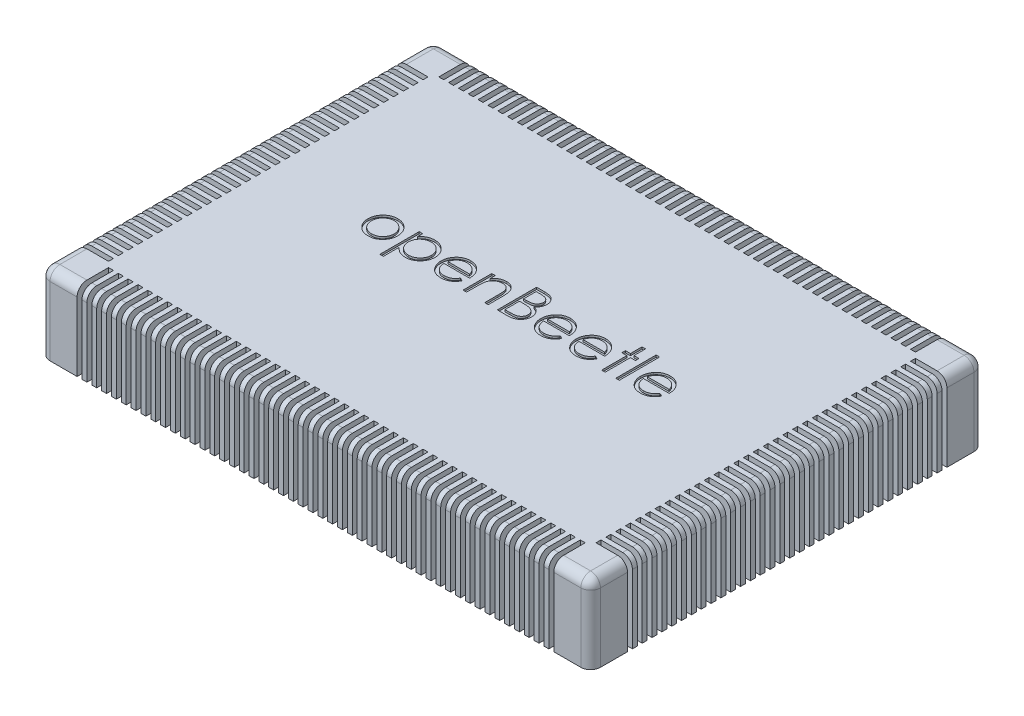
SolidWorks part; units mm, degrees
material "6061-T4 (SS)"
ref_plane "Front Plane" through (0, 0, 0) normal (0, 0, 1) x (1, 0, 0)
ref_plane "Top Plane" through (0, 0, 0) normal (0, 1, 0) x (1, 0, 0)
ref_plane "Right Plane" through (0, 0, 0) normal (1, 0, 0) x (0, 0, -1)
sketch "Sketch1" plane through (0, 0, 0) normal (0, 1, 0) x (1, 0, 0)
  line L0 (-12.7, -12.7) -> (-12.7, 114.3)
  line L1 (0, 0) -> (152.4, 0)
  line L2 (0, 0) -> (0, 101.6)
  line L3 (0, 101.6) -> (152.4, 101.6)
  line L4 (152.4, 0) -> (152.4, 101.6)
  line L5 (-12.7, 114.3) -> (165.1, 114.3)
  line L6 (165.1, -12.7) -> (165.1, 114.3)
  line L7 (-12.7, -12.7) -> (165.1, -12.7)
extrude "Boss-Extrude1" add sketch "Sketch1" along normal blind 12.7
extrude "Boss-Extrude2" add sketch "Sketch1<2>" along normal blind 12.7 from surface contours L7 L6 L5 L0 starting at face at (76.2, 12.7, -50.8)
sketch "Sketch1<2>" plane through (0, 0, 0) normal (0, 1, 0) x (1, 0, 0) same geometry as "Sketch1"
fillet "Fillet4" radius 3.175 8 edges at (165.1, 12.7, 12.7) (-12.7, 12.7, -114.3) (165.1, 12.7, -114.3) (165.1, 25.4, -50.8) (76.2, 25.4, -114.3) (-12.7, 25.4, -50.8) (-12.7, 12.7, 12.7) (76.2, 25.4, 12.7)
sketch "Sketch3" plane through (0, 0, 0) normal (0, 1, 0) x (1, 0, 0)
  line L0 (0.7938, -12.7) -> (0.7938, -2.54)
  line L1 (75.4062, 114.3) -> (76.9938, 114.3)
  line L2 (75.4062, 114.3) -> (75.4062, 104.14)
  line L3 (75.4062, 104.14) -> (76.9938, 104.14)
  line L4 (76.9938, 114.3) -> (76.9938, 104.14)
  line L5 (165.1, 50.0063) -> (154.94, 50.0063)
  line L6 (165.1, 50.0063) -> (165.1, 51.5938)
  line L7 (165.1, 51.5938) -> (154.94, 51.5938)
  line L8 (154.94, 50.0063) -> (154.94, 51.5938)
  line L13 (-0.7938, -2.54) -> (0.7938, -2.54)
  line L14 (-0.7938, -12.7) -> (-0.7938, -2.54)
  line L15 (-0.7938, -12.7) -> (0.7938, -12.7)
  line L16 (76.2, 114.3) -> (76.2, -12.7) construction
  line L17 (165.1, 50.8) -> (-12.7, 50.8) construction
  line L18 (78.5812, 114.3) -> (80.1688, 114.3)
  line L19 (78.5812, 114.3) -> (78.5812, 104.14)
  line L20 (78.5812, 104.14) -> (80.1688, 104.14)
  line L21 (80.1688, 114.3) -> (80.1688, 104.14)
  line L22 (81.7562, 114.3) -> (83.3438, 114.3)
  line L23 (81.7562, 114.3) -> (81.7562, 104.14)
  line L24 (81.7562, 104.14) -> (83.3438, 104.14)
  line L25 (83.3438, 114.3) -> (83.3438, 104.14)
  line L26 (84.9312, 114.3) -> (86.5188, 114.3)
  line L27 (84.9312, 114.3) -> (84.9312, 104.14)
  line L28 (84.9312, 104.14) -> (86.5188, 104.14)
  line L29 (86.5188, 114.3) -> (86.5188, 104.14)
  line L30 (88.1062, 114.3) -> (89.6938, 114.3)
  line L31 (88.1062, 114.3) -> (88.1062, 104.14)
  line L32 (88.1062, 104.14) -> (89.6938, 104.14)
  line L33 (89.6938, 114.3) -> (89.6938, 104.14)
  line L34 (91.2812, 114.3) -> (92.8688, 114.3)
  line L35 (91.2812, 114.3) -> (91.2812, 104.14)
  line L36 (91.2812, 104.14) -> (92.8688, 104.14)
  line L37 (92.8688, 114.3) -> (92.8688, 104.14)
  line L38 (94.4562, 114.3) -> (96.0438, 114.3)
  line L39 (94.4562, 114.3) -> (94.4562, 104.14)
  line L40 (94.4562, 104.14) -> (96.0438, 104.14)
  line L41 (96.0438, 114.3) -> (96.0438, 104.14)
  line L42 (97.6312, 114.3) -> (99.2188, 114.3)
  line L43 (97.6312, 114.3) -> (97.6312, 104.14)
  line L44 (97.6312, 104.14) -> (99.2188, 104.14)
  line L45 (99.2188, 114.3) -> (99.2188, 104.14)
  line L46 (100.8062, 114.3) -> (102.3938, 114.3)
  line L47 (100.8062, 114.3) -> (100.8062, 104.14)
  line L48 (100.8062, 104.14) -> (102.3938, 104.14)
  line L49 (102.3938, 114.3) -> (102.3938, 104.14)
  line L50 (103.9812, 114.3) -> (105.5688, 114.3)
  line L51 (103.9812, 114.3) -> (103.9812, 104.14)
  line L52 (103.9812, 104.14) -> (105.5688, 104.14)
  line L53 (105.5688, 114.3) -> (105.5688, 104.14)
  line L54 (107.1562, 114.3) -> (108.7438, 114.3)
  line L55 (107.1562, 114.3) -> (107.1562, 104.14)
  line L56 (107.1562, 104.14) -> (108.7438, 104.14)
  line L57 (108.7438, 114.3) -> (108.7438, 104.14)
  line L58 (110.3312, 114.3) -> (111.9188, 114.3)
  line L59 (110.3312, 114.3) -> (110.3312, 104.14)
  line L60 (110.3312, 104.14) -> (111.9188, 104.14)
  line L61 (111.9188, 114.3) -> (111.9188, 104.14)
  line L62 (113.5062, 114.3) -> (115.0938, 114.3)
  line L63 (113.5062, 114.3) -> (113.5062, 104.14)
  line L64 (113.5062, 104.14) -> (115.0938, 104.14)
  line L65 (115.0938, 114.3) -> (115.0938, 104.14)
  line L66 (116.6812, 114.3) -> (118.2688, 114.3)
  line L67 (116.6812, 114.3) -> (116.6812, 104.14)
  line L68 (116.6812, 104.14) -> (118.2688, 104.14)
  line L69 (118.2688, 114.3) -> (118.2688, 104.14)
  line L70 (119.8562, 114.3) -> (121.4438, 114.3)
  line L71 (119.8562, 114.3) -> (119.8562, 104.14)
  line L72 (119.8562, 104.14) -> (121.4438, 104.14)
  line L73 (121.4438, 114.3) -> (121.4438, 104.14)
  line L74 (123.0312, 114.3) -> (124.6188, 114.3)
  line L75 (123.0312, 114.3) -> (123.0312, 104.14)
  line L76 (123.0312, 104.14) -> (124.6188, 104.14)
  line L77 (124.6188, 114.3) -> (124.6188, 104.14)
  line L78 (126.2062, 114.3) -> (127.7938, 114.3)
  line L79 (126.2062, 114.3) -> (126.2062, 104.14)
  line L80 (126.2062, 104.14) -> (127.7938, 104.14)
  line L81 (127.7938, 114.3) -> (127.7938, 104.14)
  line L82 (129.3812, 114.3) -> (130.9688, 114.3)
  line L83 (129.3812, 114.3) -> (129.3812, 104.14)
  line L84 (129.3812, 104.14) -> (130.9688, 104.14)
  line L85 (130.9688, 114.3) -> (130.9688, 104.14)
  line L86 (132.5562, 114.3) -> (134.1438, 114.3)
  line L87 (132.5562, 114.3) -> (132.5562, 104.14)
  line L88 (132.5562, 104.14) -> (134.1438, 104.14)
  line L89 (134.1438, 114.3) -> (134.1438, 104.14)
  line L90 (135.7312, 114.3) -> (137.3188, 114.3)
  line L91 (135.7312, 114.3) -> (135.7312, 104.14)
  line L92 (135.7312, 104.14) -> (137.3188, 104.14)
  line L93 (137.3188, 114.3) -> (137.3188, 104.14)
  line L94 (138.9062, 114.3) -> (140.4938, 114.3)
  line L95 (138.9062, 114.3) -> (138.9062, 104.14)
  line L96 (138.9062, 104.14) -> (140.4938, 104.14)
  line L97 (140.4938, 114.3) -> (140.4938, 104.14)
  line L98 (142.0812, 114.3) -> (143.6688, 114.3)
  line L99 (142.0812, 114.3) -> (142.0812, 104.14)
  line L100 (142.0812, 104.14) -> (143.6688, 104.14)
  line L101 (143.6688, 114.3) -> (143.6688, 104.14)
  line L102 (145.2562, 114.3) -> (146.8438, 114.3)
  line L103 (145.2562, 114.3) -> (145.2562, 104.14)
  line L104 (145.2562, 104.14) -> (146.8438, 104.14)
  line L105 (146.8438, 114.3) -> (146.8438, 104.14)
  line L106 (148.4312, 114.3) -> (150.0188, 114.3)
  line L107 (148.4312, 114.3) -> (148.4312, 104.14)
  line L108 (148.4312, 104.14) -> (150.0188, 104.14)
  line L109 (150.0188, 114.3) -> (150.0188, 104.14)
  line L110 (151.6062, 114.3) -> (153.1938, 114.3)
  line L111 (151.6062, 114.3) -> (151.6062, 104.14)
  line L112 (151.6062, 104.14) -> (153.1938, 104.14)
  line L113 (153.1938, 114.3) -> (153.1938, 104.14)
  line L114 (72.2312, 114.3) -> (73.8188, 114.3)
  line L115 (72.2312, 114.3) -> (72.2312, 104.14)
  line L116 (72.2312, 104.14) -> (73.8188, 104.14)
  line L117 (73.8188, 114.3) -> (73.8188, 104.14)
  line L118 (69.0562, 114.3) -> (70.6438, 114.3)
  line L119 (69.0562, 114.3) -> (69.0562, 104.14)
  line L120 (69.0562, 104.14) -> (70.6438, 104.14)
  line L121 (70.6438, 114.3) -> (70.6438, 104.14)
  line L122 (65.8812, 114.3) -> (67.4688, 114.3)
  line L123 (65.8812, 114.3) -> (65.8812, 104.14)
  line L124 (65.8812, 104.14) -> (67.4688, 104.14)
  line L125 (67.4688, 114.3) -> (67.4688, 104.14)
  line L126 (62.7062, 114.3) -> (64.2938, 114.3)
  line L127 (62.7062, 114.3) -> (62.7062, 104.14)
  line L128 (62.7062, 104.14) -> (64.2938, 104.14)
  line L129 (64.2938, 114.3) -> (64.2938, 104.14)
  line L130 (59.5312, 114.3) -> (61.1188, 114.3)
  line L131 (59.5312, 114.3) -> (59.5312, 104.14)
  line L132 (59.5312, 104.14) -> (61.1188, 104.14)
  line L133 (61.1188, 114.3) -> (61.1188, 104.14)
  line L134 (56.3562, 114.3) -> (57.9438, 114.3)
  line L135 (56.3562, 114.3) -> (56.3562, 104.14)
  line L136 (56.3562, 104.14) -> (57.9438, 104.14)
  line L137 (57.9438, 114.3) -> (57.9438, 104.14)
  line L138 (53.1812, 114.3) -> (54.7688, 114.3)
  line L139 (53.1812, 114.3) -> (53.1812, 104.14)
  line L140 (53.1812, 104.14) -> (54.7688, 104.14)
  line L141 (54.7688, 114.3) -> (54.7688, 104.14)
  line L142 (50.0062, 114.3) -> (51.5938, 114.3)
  line L143 (50.0062, 114.3) -> (50.0062, 104.14)
  line L144 (50.0062, 104.14) -> (51.5938, 104.14)
  line L145 (51.5938, 114.3) -> (51.5938, 104.14)
  line L146 (46.8312, 114.3) -> (48.4188, 114.3)
  line L147 (46.8312, 114.3) -> (46.8312, 104.14)
  line L148 (46.8312, 104.14) -> (48.4188, 104.14)
  line L149 (48.4188, 114.3) -> (48.4188, 104.14)
  line L150 (43.6562, 114.3) -> (45.2438, 114.3)
  line L151 (43.6562, 114.3) -> (43.6562, 104.14)
  line L152 (43.6562, 104.14) -> (45.2438, 104.14)
  line L153 (45.2438, 114.3) -> (45.2438, 104.14)
  line L154 (40.4812, 114.3) -> (42.0688, 114.3)
  line L155 (40.4812, 114.3) -> (40.4812, 104.14)
  line L156 (40.4812, 104.14) -> (42.0688, 104.14)
  line L157 (42.0688, 114.3) -> (42.0688, 104.14)
  line L158 (37.3062, 114.3) -> (38.8938, 114.3)
  line L159 (37.3062, 114.3) -> (37.3062, 104.14)
  line L160 (37.3062, 104.14) -> (38.8938, 104.14)
  line L161 (38.8938, 114.3) -> (38.8938, 104.14)
  line L162 (34.1312, 114.3) -> (35.7188, 114.3)
  line L163 (34.1312, 114.3) -> (34.1312, 104.14)
  line L164 (34.1312, 104.14) -> (35.7188, 104.14)
  line L165 (35.7188, 114.3) -> (35.7188, 104.14)
  line L166 (30.9562, 114.3) -> (32.5438, 114.3)
  line L167 (30.9562, 114.3) -> (30.9562, 104.14)
  line L168 (30.9562, 104.14) -> (32.5438, 104.14)
  line L169 (32.5438, 114.3) -> (32.5438, 104.14)
  line L170 (27.7812, 114.3) -> (29.3688, 114.3)
  line L171 (27.7812, 114.3) -> (27.7812, 104.14)
  line L172 (27.7812, 104.14) -> (29.3688, 104.14)
  line L173 (29.3688, 114.3) -> (29.3688, 104.14)
  line L174 (24.6062, 114.3) -> (26.1938, 114.3)
  line L175 (24.6062, 114.3) -> (24.6062, 104.14)
  line L176 (24.6062, 104.14) -> (26.1938, 104.14)
  line L177 (26.1938, 114.3) -> (26.1938, 104.14)
  line L178 (21.4312, 114.3) -> (23.0188, 114.3)
  line L179 (21.4312, 114.3) -> (21.4312, 104.14)
  line L180 (21.4312, 104.14) -> (23.0188, 104.14)
  line L181 (23.0188, 114.3) -> (23.0188, 104.14)
  line L182 (18.2562, 114.3) -> (19.8438, 114.3)
  line L183 (18.2562, 114.3) -> (18.2562, 104.14)
  line L184 (18.2562, 104.14) -> (19.8438, 104.14)
  line L185 (19.8438, 114.3) -> (19.8438, 104.14)
  line L186 (15.0812, 114.3) -> (16.6688, 114.3)
  line L187 (15.0812, 114.3) -> (15.0812, 104.14)
  line L188 (15.0812, 104.14) -> (16.6688, 104.14)
  line L189 (16.6688, 114.3) -> (16.6688, 104.14)
  line L190 (11.9062, 114.3) -> (13.4938, 114.3)
  line L191 (11.9062, 114.3) -> (11.9062, 104.14)
  line L192 (11.9062, 104.14) -> (13.4938, 104.14)
  line L193 (13.4938, 114.3) -> (13.4938, 104.14)
  line L194 (8.7312, 114.3) -> (10.3188, 114.3)
  line L195 (8.7312, 114.3) -> (8.7312, 104.14)
  line L196 (8.7312, 104.14) -> (10.3188, 104.14)
  line L197 (10.3188, 114.3) -> (10.3188, 104.14)
  line L198 (5.5562, 114.3) -> (7.1438, 114.3)
  line L199 (5.5562, 114.3) -> (5.5562, 104.14)
  line L200 (5.5562, 104.14) -> (7.1438, 104.14)
  line L201 (7.1438, 114.3) -> (7.1438, 104.14)
  line L202 (2.3812, 114.3) -> (3.9688, 114.3)
  line L203 (2.3812, 114.3) -> (2.3812, 104.14)
  line L204 (2.3812, 104.14) -> (3.9688, 104.14)
  line L205 (3.9688, 114.3) -> (3.9688, 104.14)
  line L206 (-0.7938, 114.3) -> (0.7938, 114.3)
  line L207 (-0.7938, 114.3) -> (-0.7938, 104.14)
  line L208 (-0.7938, 104.14) -> (0.7938, 104.14)
  line L209 (0.7938, 114.3) -> (0.7938, 104.14)
  line L210 (165.1, 53.1813) -> (154.94, 53.1813)
  line L211 (165.1, 53.1813) -> (165.1, 54.7688)
  line L212 (165.1, 54.7688) -> (154.94, 54.7688)
  line L213 (154.94, 53.1813) -> (154.94, 54.7688)
  line L214 (165.1, 56.3563) -> (154.94, 56.3563)
  line L215 (165.1, 56.3563) -> (165.1, 57.9438)
  line L216 (165.1, 57.9438) -> (154.94, 57.9438)
  line L217 (154.94, 56.3563) -> (154.94, 57.9438)
  line L218 (165.1, 59.5313) -> (154.94, 59.5313)
  line L219 (165.1, 59.5313) -> (165.1, 61.1188)
  line L220 (165.1, 61.1188) -> (154.94, 61.1188)
  line L221 (154.94, 59.5313) -> (154.94, 61.1188)
  line L222 (165.1, 62.7063) -> (154.94, 62.7063)
  line L223 (165.1, 62.7063) -> (165.1, 64.2938)
  line L224 (165.1, 64.2938) -> (154.94, 64.2938)
  line L225 (154.94, 62.7063) -> (154.94, 64.2938)
  line L226 (165.1, 65.8813) -> (154.94, 65.8813)
  line L227 (165.1, 65.8813) -> (165.1, 67.4688)
  line L228 (165.1, 67.4688) -> (154.94, 67.4688)
  line L229 (154.94, 65.8813) -> (154.94, 67.4688)
  line L230 (165.1, 69.0563) -> (154.94, 69.0563)
  line L231 (165.1, 69.0563) -> (165.1, 70.6438)
  line L232 (165.1, 70.6438) -> (154.94, 70.6438)
  line L233 (154.94, 69.0563) -> (154.94, 70.6438)
  line L234 (165.1, 72.2313) -> (154.94, 72.2313)
  line L235 (165.1, 72.2313) -> (165.1, 73.8188)
  line L236 (165.1, 73.8188) -> (154.94, 73.8188)
  line L237 (154.94, 72.2313) -> (154.94, 73.8188)
  line L238 (165.1, 75.4063) -> (154.94, 75.4063)
  line L239 (165.1, 75.4063) -> (165.1, 76.9938)
  line L240 (165.1, 76.9938) -> (154.94, 76.9938)
  line L241 (154.94, 75.4063) -> (154.94, 76.9938)
  line L242 (165.1, 78.5813) -> (154.94, 78.5813)
  line L243 (165.1, 78.5813) -> (165.1, 80.1688)
  line L244 (165.1, 80.1688) -> (154.94, 80.1688)
  line L245 (154.94, 78.5813) -> (154.94, 80.1688)
  line L246 (165.1, 81.7563) -> (154.94, 81.7563)
  line L247 (165.1, 81.7563) -> (165.1, 83.3438)
  line L248 (165.1, 83.3438) -> (154.94, 83.3438)
  line L249 (154.94, 81.7563) -> (154.94, 83.3438)
  line L250 (165.1, 84.9313) -> (154.94, 84.9313)
  line L251 (165.1, 84.9313) -> (165.1, 86.5188)
  line L252 (165.1, 86.5188) -> (154.94, 86.5188)
  line L253 (154.94, 84.9313) -> (154.94, 86.5188)
  line L254 (165.1, 88.1063) -> (154.94, 88.1063)
  line L255 (165.1, 88.1063) -> (165.1, 89.6938)
  line L256 (165.1, 89.6938) -> (154.94, 89.6938)
  line L257 (154.94, 88.1063) -> (154.94, 89.6938)
  line L258 (165.1, 91.2813) -> (154.94, 91.2813)
  line L259 (165.1, 91.2813) -> (165.1, 92.8688)
  line L260 (165.1, 92.8688) -> (154.94, 92.8688)
  line L261 (154.94, 91.2813) -> (154.94, 92.8688)
  line L262 (165.1, 94.4563) -> (154.94, 94.4563)
  line L263 (165.1, 94.4563) -> (165.1, 96.0438)
  line L264 (165.1, 96.0438) -> (154.94, 96.0438)
  line L265 (154.94, 94.4563) -> (154.94, 96.0438)
  line L266 (165.1, 97.6313) -> (154.94, 97.6313)
  line L267 (165.1, 97.6313) -> (165.1, 99.2188)
  line L268 (165.1, 99.2188) -> (154.94, 99.2188)
  line L269 (154.94, 97.6313) -> (154.94, 99.2188)
  line L270 (165.1, 100.8063) -> (154.94, 100.8063)
  line L271 (165.1, 100.8063) -> (165.1, 102.3938)
  line L272 (165.1, 102.3938) -> (154.94, 102.3938)
  line L273 (154.94, 100.8063) -> (154.94, 102.3938)
  line L274 (165.1, 46.8313) -> (154.94, 46.8313)
  line L275 (165.1, 46.8313) -> (165.1, 48.4188)
  line L276 (165.1, 48.4188) -> (154.94, 48.4188)
  line L277 (154.94, 46.8313) -> (154.94, 48.4188)
  line L278 (165.1, 43.6563) -> (154.94, 43.6563)
  line L279 (165.1, 43.6563) -> (165.1, 45.2438)
  line L280 (165.1, 45.2438) -> (154.94, 45.2438)
  line L281 (154.94, 43.6563) -> (154.94, 45.2438)
  line L282 (165.1, 40.4813) -> (154.94, 40.4813)
  line L283 (165.1, 40.4813) -> (165.1, 42.0688)
  line L284 (165.1, 42.0688) -> (154.94, 42.0688)
  line L285 (154.94, 40.4813) -> (154.94, 42.0688)
  line L286 (165.1, 37.3063) -> (154.94, 37.3063)
  line L287 (165.1, 37.3063) -> (165.1, 38.8938)
  line L288 (165.1, 38.8938) -> (154.94, 38.8938)
  line L289 (154.94, 37.3063) -> (154.94, 38.8938)
  line L290 (165.1, 34.1313) -> (154.94, 34.1313)
  line L291 (165.1, 34.1313) -> (165.1, 35.7188)
  line L292 (165.1, 35.7188) -> (154.94, 35.7188)
  line L293 (154.94, 34.1313) -> (154.94, 35.7188)
  line L294 (165.1, 30.9563) -> (154.94, 30.9563)
  line L295 (165.1, 30.9563) -> (165.1, 32.5438)
  line L296 (165.1, 32.5438) -> (154.94, 32.5438)
  line L297 (154.94, 30.9563) -> (154.94, 32.5438)
  line L298 (165.1, 27.7813) -> (154.94, 27.7813)
  line L299 (165.1, 27.7813) -> (165.1, 29.3688)
  line L300 (165.1, 29.3688) -> (154.94, 29.3688)
  line L301 (154.94, 27.7813) -> (154.94, 29.3688)
  line L302 (165.1, 24.6063) -> (154.94, 24.6063)
  line L303 (165.1, 24.6063) -> (165.1, 26.1938)
  line L304 (165.1, 26.1938) -> (154.94, 26.1938)
  line L305 (154.94, 24.6063) -> (154.94, 26.1938)
  line L306 (165.1, 21.4313) -> (154.94, 21.4313)
  line L307 (165.1, 21.4313) -> (165.1, 23.0188)
  line L308 (165.1, 23.0188) -> (154.94, 23.0188)
  line L309 (154.94, 21.4313) -> (154.94, 23.0188)
  line L310 (165.1, 18.2563) -> (154.94, 18.2563)
  line L311 (165.1, 18.2563) -> (165.1, 19.8438)
  line L312 (165.1, 19.8438) -> (154.94, 19.8438)
  line L313 (154.94, 18.2563) -> (154.94, 19.8438)
  line L314 (165.1, 15.0813) -> (154.94, 15.0813)
  line L315 (165.1, 15.0813) -> (165.1, 16.6688)
  line L316 (165.1, 16.6688) -> (154.94, 16.6688)
  line L317 (154.94, 15.0813) -> (154.94, 16.6688)
  line L318 (165.1, 11.9063) -> (154.94, 11.9063)
  line L319 (165.1, 11.9063) -> (165.1, 13.4938)
  line L320 (165.1, 13.4938) -> (154.94, 13.4938)
  line L321 (154.94, 11.9063) -> (154.94, 13.4938)
  line L322 (165.1, 8.7313) -> (154.94, 8.7313)
  line L323 (165.1, 8.7313) -> (165.1, 10.3188)
  line L324 (165.1, 10.3188) -> (154.94, 10.3188)
  line L325 (154.94, 8.7313) -> (154.94, 10.3188)
  line L326 (165.1, 5.5563) -> (154.94, 5.5563)
  line L327 (165.1, 5.5563) -> (165.1, 7.1438)
  line L328 (165.1, 7.1438) -> (154.94, 7.1438)
  line L329 (154.94, 5.5563) -> (154.94, 7.1438)
  line L330 (165.1, 2.3813) -> (154.94, 2.3813)
  line L331 (165.1, 2.3813) -> (165.1, 3.9688)
  line L332 (165.1, 3.9688) -> (154.94, 3.9688)
  line L333 (154.94, 2.3813) -> (154.94, 3.9688)
  line L334 (165.1, -0.7937) -> (154.94, -0.7937)
  line L335 (165.1, -0.7937) -> (165.1, 0.7938)
  line L336 (165.1, 0.7938) -> (154.94, 0.7938)
  line L337 (154.94, -0.7937) -> (154.94, 0.7938)
  line L338 (3.9688, -12.7) -> (3.9688, -2.54)
  line L339 (2.3812, -2.54) -> (3.9688, -2.54)
  line L340 (2.3812, -12.7) -> (2.3812, -2.54)
  line L341 (2.3812, -12.7) -> (3.9688, -12.7)
  line L342 (7.1438, -12.7) -> (7.1438, -2.54)
  line L343 (5.5562, -2.54) -> (7.1438, -2.54)
  line L344 (5.5562, -12.7) -> (5.5562, -2.54)
  line L345 (5.5562, -12.7) -> (7.1438, -12.7)
  line L346 (10.3188, -12.7) -> (10.3188, -2.54)
  line L347 (8.7312, -2.54) -> (10.3188, -2.54)
  line L348 (8.7312, -12.7) -> (8.7312, -2.54)
  line L349 (8.7312, -12.7) -> (10.3188, -12.7)
  line L350 (13.4938, -12.7) -> (13.4938, -2.54)
  line L351 (11.9062, -2.54) -> (13.4938, -2.54)
  line L352 (11.9062, -12.7) -> (11.9062, -2.54)
  line L353 (11.9062, -12.7) -> (13.4938, -12.7)
  line L354 (16.6688, -12.7) -> (16.6688, -2.54)
  line L355 (15.0812, -2.54) -> (16.6688, -2.54)
  line L356 (15.0812, -12.7) -> (15.0812, -2.54)
  line L357 (15.0812, -12.7) -> (16.6688, -12.7)
  line L358 (19.8438, -12.7) -> (19.8438, -2.54)
  line L359 (18.2562, -2.54) -> (19.8438, -2.54)
  line L360 (18.2562, -12.7) -> (18.2562, -2.54)
  line L361 (18.2562, -12.7) -> (19.8438, -12.7)
  line L362 (23.0188, -12.7) -> (23.0188, -2.54)
  line L363 (21.4312, -2.54) -> (23.0188, -2.54)
  line L364 (21.4312, -12.7) -> (21.4312, -2.54)
  line L365 (21.4312, -12.7) -> (23.0188, -12.7)
  line L366 (26.1938, -12.7) -> (26.1938, -2.54)
  line L367 (24.6062, -2.54) -> (26.1938, -2.54)
  line L368 (24.6062, -12.7) -> (24.6062, -2.54)
  line L369 (24.6062, -12.7) -> (26.1938, -12.7)
  line L370 (29.3688, -12.7) -> (29.3688, -2.54)
  line L371 (27.7812, -2.54) -> (29.3688, -2.54)
  line L372 (27.7812, -12.7) -> (27.7812, -2.54)
  line L373 (27.7812, -12.7) -> (29.3688, -12.7)
  line L374 (32.5438, -12.7) -> (32.5438, -2.54)
  line L375 (30.9562, -2.54) -> (32.5438, -2.54)
  line L376 (30.9562, -12.7) -> (30.9562, -2.54)
  line L377 (30.9562, -12.7) -> (32.5438, -12.7)
  line L378 (35.7188, -12.7) -> (35.7188, -2.54)
  line L379 (34.1312, -2.54) -> (35.7188, -2.54)
  line L380 (34.1312, -12.7) -> (34.1312, -2.54)
  line L381 (34.1312, -12.7) -> (35.7188, -12.7)
  line L382 (38.8938, -12.7) -> (38.8938, -2.54)
  line L383 (37.3062, -2.54) -> (38.8938, -2.54)
  line L384 (37.3062, -12.7) -> (37.3062, -2.54)
  line L385 (37.3062, -12.7) -> (38.8938, -12.7)
  line L386 (42.0688, -12.7) -> (42.0688, -2.54)
  line L387 (40.4812, -2.54) -> (42.0688, -2.54)
  line L388 (40.4812, -12.7) -> (40.4812, -2.54)
  line L389 (40.4812, -12.7) -> (42.0688, -12.7)
  line L390 (45.2438, -12.7) -> (45.2438, -2.54)
  line L391 (43.6562, -2.54) -> (45.2438, -2.54)
  line L392 (43.6562, -12.7) -> (43.6562, -2.54)
  line L393 (43.6562, -12.7) -> (45.2438, -12.7)
  line L394 (48.4188, -12.7) -> (48.4188, -2.54)
  line L395 (46.8312, -2.54) -> (48.4188, -2.54)
  line L396 (46.8312, -12.7) -> (46.8312, -2.54)
  line L397 (46.8312, -12.7) -> (48.4188, -12.7)
  line L398 (51.5938, -12.7) -> (51.5938, -2.54)
  line L399 (50.0062, -2.54) -> (51.5938, -2.54)
  line L400 (50.0062, -12.7) -> (50.0062, -2.54)
  line L401 (50.0062, -12.7) -> (51.5938, -12.7)
  line L402 (54.7688, -12.7) -> (54.7688, -2.54)
  line L403 (53.1812, -2.54) -> (54.7688, -2.54)
  line L404 (53.1812, -12.7) -> (53.1812, -2.54)
  line L405 (53.1812, -12.7) -> (54.7688, -12.7)
  line L406 (57.9438, -12.7) -> (57.9438, -2.54)
  line L407 (56.3562, -2.54) -> (57.9438, -2.54)
  line L408 (56.3562, -12.7) -> (56.3562, -2.54)
  line L409 (56.3562, -12.7) -> (57.9438, -12.7)
  line L410 (61.1188, -12.7) -> (61.1188, -2.54)
  line L411 (59.5312, -2.54) -> (61.1188, -2.54)
  line L412 (59.5312, -12.7) -> (59.5312, -2.54)
  line L413 (59.5312, -12.7) -> (61.1188, -12.7)
  line L414 (64.2938, -12.7) -> (64.2938, -2.54)
  line L415 (62.7062, -2.54) -> (64.2938, -2.54)
  line L416 (62.7062, -12.7) -> (62.7062, -2.54)
  line L417 (62.7062, -12.7) -> (64.2938, -12.7)
  line L418 (67.4688, -12.7) -> (67.4688, -2.54)
  line L419 (65.8812, -2.54) -> (67.4688, -2.54)
  line L420 (65.8812, -12.7) -> (65.8812, -2.54)
  line L421 (65.8812, -12.7) -> (67.4688, -12.7)
  line L422 (70.6438, -12.7) -> (70.6438, -2.54)
  line L423 (69.0562, -2.54) -> (70.6438, -2.54)
  line L424 (69.0562, -12.7) -> (69.0562, -2.54)
  line L425 (69.0562, -12.7) -> (70.6438, -12.7)
  line L426 (73.8188, -12.7) -> (73.8188, -2.54)
  line L427 (72.2312, -2.54) -> (73.8188, -2.54)
  line L428 (72.2312, -12.7) -> (72.2312, -2.54)
  line L429 (72.2312, -12.7) -> (73.8188, -12.7)
  line L430 (153.1938, -12.7) -> (153.1938, -2.54)
  line L431 (151.6062, -2.54) -> (153.1938, -2.54)
  line L432 (151.6062, -12.7) -> (151.6062, -2.54)
  line L433 (151.6062, -12.7) -> (153.1938, -12.7)
  line L434 (150.0188, -12.7) -> (150.0188, -2.54)
  line L435 (148.4312, -2.54) -> (150.0188, -2.54)
  line L436 (148.4312, -12.7) -> (148.4312, -2.54)
  line L437 (148.4312, -12.7) -> (150.0188, -12.7)
  line L438 (146.8438, -12.7) -> (146.8438, -2.54)
  line L439 (145.2562, -2.54) -> (146.8438, -2.54)
  line L440 (145.2562, -12.7) -> (145.2562, -2.54)
  line L441 (145.2562, -12.7) -> (146.8438, -12.7)
  line L442 (143.6688, -12.7) -> (143.6688, -2.54)
  line L443 (142.0812, -2.54) -> (143.6688, -2.54)
  line L444 (142.0812, -12.7) -> (142.0812, -2.54)
  line L445 (142.0812, -12.7) -> (143.6688, -12.7)
  line L446 (140.4938, -12.7) -> (140.4938, -2.54)
  line L447 (138.9062, -2.54) -> (140.4938, -2.54)
  line L448 (138.9062, -12.7) -> (138.9062, -2.54)
  line L449 (138.9062, -12.7) -> (140.4938, -12.7)
  line L450 (137.3188, -12.7) -> (137.3188, -2.54)
  line L451 (135.7312, -2.54) -> (137.3188, -2.54)
  line L452 (135.7312, -12.7) -> (135.7312, -2.54)
  line L453 (135.7312, -12.7) -> (137.3188, -12.7)
  line L454 (134.1438, -12.7) -> (134.1438, -2.54)
  line L455 (132.5562, -2.54) -> (134.1438, -2.54)
  line L456 (132.5562, -12.7) -> (132.5562, -2.54)
  line L457 (132.5562, -12.7) -> (134.1438, -12.7)
  line L458 (130.9688, -12.7) -> (130.9688, -2.54)
  line L459 (129.3812, -2.54) -> (130.9688, -2.54)
  line L460 (129.3812, -12.7) -> (129.3812, -2.54)
  line L461 (129.3812, -12.7) -> (130.9688, -12.7)
  line L462 (127.7938, -12.7) -> (127.7938, -2.54)
  line L463 (126.2062, -2.54) -> (127.7938, -2.54)
  line L464 (126.2062, -12.7) -> (126.2062, -2.54)
  line L465 (126.2062, -12.7) -> (127.7938, -12.7)
  line L466 (124.6188, -12.7) -> (124.6188, -2.54)
  line L467 (123.0312, -2.54) -> (124.6188, -2.54)
  line L468 (123.0312, -12.7) -> (123.0312, -2.54)
  line L469 (123.0312, -12.7) -> (124.6188, -12.7)
  line L470 (121.4438, -12.7) -> (121.4438, -2.54)
  line L471 (119.8562, -2.54) -> (121.4438, -2.54)
  line L472 (119.8562, -12.7) -> (119.8562, -2.54)
  line L473 (119.8562, -12.7) -> (121.4438, -12.7)
  line L474 (118.2688, -12.7) -> (118.2688, -2.54)
  line L475 (116.6812, -2.54) -> (118.2688, -2.54)
  line L476 (116.6812, -12.7) -> (116.6812, -2.54)
  line L477 (116.6812, -12.7) -> (118.2688, -12.7)
  line L478 (115.0938, -12.7) -> (115.0938, -2.54)
  line L479 (113.5062, -2.54) -> (115.0938, -2.54)
  line L480 (113.5062, -12.7) -> (113.5062, -2.54)
  line L481 (113.5062, -12.7) -> (115.0938, -12.7)
  line L482 (111.9188, -12.7) -> (111.9188, -2.54)
  line L483 (110.3312, -2.54) -> (111.9188, -2.54)
  line L484 (110.3312, -12.7) -> (110.3312, -2.54)
  line L485 (110.3312, -12.7) -> (111.9188, -12.7)
  line L486 (108.7438, -12.7) -> (108.7438, -2.54)
  line L487 (107.1562, -2.54) -> (108.7438, -2.54)
  line L488 (107.1562, -12.7) -> (107.1562, -2.54)
  line L489 (107.1562, -12.7) -> (108.7438, -12.7)
  line L490 (105.5688, -12.7) -> (105.5688, -2.54)
  line L491 (103.9812, -2.54) -> (105.5688, -2.54)
  line L492 (103.9812, -12.7) -> (103.9812, -2.54)
  line L493 (103.9812, -12.7) -> (105.5688, -12.7)
  line L494 (102.3938, -12.7) -> (102.3938, -2.54)
  line L495 (100.8062, -2.54) -> (102.3938, -2.54)
  line L496 (100.8062, -12.7) -> (100.8062, -2.54)
  line L497 (100.8062, -12.7) -> (102.3938, -12.7)
  line L498 (99.2188, -12.7) -> (99.2188, -2.54)
  line L499 (97.6312, -2.54) -> (99.2188, -2.54)
  line L500 (97.6312, -12.7) -> (97.6312, -2.54)
  line L501 (97.6312, -12.7) -> (99.2188, -12.7)
  line L502 (96.0438, -12.7) -> (96.0438, -2.54)
  line L503 (94.4562, -2.54) -> (96.0438, -2.54)
  line L504 (94.4562, -12.7) -> (94.4562, -2.54)
  line L505 (94.4562, -12.7) -> (96.0438, -12.7)
  line L506 (92.8688, -12.7) -> (92.8688, -2.54)
  line L507 (91.2812, -2.54) -> (92.8688, -2.54)
  line L508 (91.2812, -12.7) -> (91.2812, -2.54)
  line L509 (91.2812, -12.7) -> (92.8688, -12.7)
  line L510 (89.6938, -12.7) -> (89.6938, -2.54)
  line L511 (88.1062, -2.54) -> (89.6938, -2.54)
  line L512 (88.1062, -12.7) -> (88.1062, -2.54)
  line L513 (88.1062, -12.7) -> (89.6938, -12.7)
  line L514 (86.5188, -12.7) -> (86.5188, -2.54)
  line L515 (84.9312, -2.54) -> (86.5188, -2.54)
  line L516 (84.9312, -12.7) -> (84.9312, -2.54)
  line L517 (84.9312, -12.7) -> (86.5188, -12.7)
  line L518 (83.3438, -12.7) -> (83.3438, -2.54)
  line L519 (81.7562, -2.54) -> (83.3438, -2.54)
  line L520 (81.7562, -12.7) -> (81.7562, -2.54)
  line L521 (81.7562, -12.7) -> (83.3438, -12.7)
  line L522 (80.1688, -12.7) -> (80.1688, -2.54)
  line L523 (78.5812, -2.54) -> (80.1688, -2.54)
  line L524 (78.5812, -12.7) -> (78.5812, -2.54)
  line L525 (78.5812, -12.7) -> (80.1688, -12.7)
  line L526 (76.9938, -12.7) -> (76.9938, -2.54)
  line L527 (75.4062, -2.54) -> (76.9938, -2.54)
  line L528 (75.4062, -12.7) -> (75.4062, -2.54)
  line L529 (75.4062, -12.7) -> (76.9938, -12.7)
  line L530 (-2.54, -0.7937) -> (-2.54, 0.7938)
  line L531 (-12.7, 0.7938) -> (-2.54, 0.7938)
  line L532 (-12.7, -0.7937) -> (-12.7, 0.7938)
  line L533 (-12.7, -0.7937) -> (-2.54, -0.7937)
  line L534 (-2.54, 2.3813) -> (-2.54, 3.9688)
  line L535 (-12.7, 3.9688) -> (-2.54, 3.9688)
  line L536 (-12.7, 2.3813) -> (-12.7, 3.9688)
  line L537 (-12.7, 2.3813) -> (-2.54, 2.3813)
  line L538 (-2.54, 5.5563) -> (-2.54, 7.1438)
  line L539 (-12.7, 7.1438) -> (-2.54, 7.1438)
  line L540 (-12.7, 5.5563) -> (-12.7, 7.1438)
  line L541 (-12.7, 5.5563) -> (-2.54, 5.5563)
  line L542 (-2.54, 8.7313) -> (-2.54, 10.3188)
  line L543 (-12.7, 10.3188) -> (-2.54, 10.3188)
  line L544 (-12.7, 8.7313) -> (-12.7, 10.3188)
  line L545 (-12.7, 8.7313) -> (-2.54, 8.7313)
  line L546 (-2.54, 11.9063) -> (-2.54, 13.4938)
  line L547 (-12.7, 13.4938) -> (-2.54, 13.4938)
  line L548 (-12.7, 11.9063) -> (-12.7, 13.4938)
  line L549 (-12.7, 11.9063) -> (-2.54, 11.9063)
  line L550 (-2.54, 15.0813) -> (-2.54, 16.6688)
  line L551 (-12.7, 16.6688) -> (-2.54, 16.6688)
  line L552 (-12.7, 15.0813) -> (-12.7, 16.6688)
  line L553 (-12.7, 15.0813) -> (-2.54, 15.0813)
  line L554 (-2.54, 18.2563) -> (-2.54, 19.8438)
  line L555 (-12.7, 19.8438) -> (-2.54, 19.8438)
  line L556 (-12.7, 18.2563) -> (-12.7, 19.8438)
  line L557 (-12.7, 18.2563) -> (-2.54, 18.2563)
  line L558 (-2.54, 21.4313) -> (-2.54, 23.0188)
  line L559 (-12.7, 23.0188) -> (-2.54, 23.0188)
  line L560 (-12.7, 21.4313) -> (-12.7, 23.0188)
  line L561 (-12.7, 21.4313) -> (-2.54, 21.4313)
  line L562 (-2.54, 24.6063) -> (-2.54, 26.1938)
  line L563 (-12.7, 26.1938) -> (-2.54, 26.1938)
  line L564 (-12.7, 24.6063) -> (-12.7, 26.1938)
  line L565 (-12.7, 24.6063) -> (-2.54, 24.6063)
  line L566 (-2.54, 27.7813) -> (-2.54, 29.3688)
  line L567 (-12.7, 29.3688) -> (-2.54, 29.3688)
  line L568 (-12.7, 27.7813) -> (-12.7, 29.3688)
  line L569 (-12.7, 27.7813) -> (-2.54, 27.7813)
  line L570 (-2.54, 30.9563) -> (-2.54, 32.5438)
  line L571 (-12.7, 32.5438) -> (-2.54, 32.5438)
  line L572 (-12.7, 30.9563) -> (-12.7, 32.5438)
  line L573 (-12.7, 30.9563) -> (-2.54, 30.9563)
  line L574 (-2.54, 34.1313) -> (-2.54, 35.7188)
  line L575 (-12.7, 35.7188) -> (-2.54, 35.7188)
  line L576 (-12.7, 34.1313) -> (-12.7, 35.7188)
  line L577 (-12.7, 34.1313) -> (-2.54, 34.1313)
  line L578 (-2.54, 37.3063) -> (-2.54, 38.8938)
  line L579 (-12.7, 38.8938) -> (-2.54, 38.8938)
  line L580 (-12.7, 37.3063) -> (-12.7, 38.8938)
  line L581 (-12.7, 37.3063) -> (-2.54, 37.3063)
  line L582 (-2.54, 40.4813) -> (-2.54, 42.0688)
  line L583 (-12.7, 42.0688) -> (-2.54, 42.0688)
  line L584 (-12.7, 40.4813) -> (-12.7, 42.0688)
  line L585 (-12.7, 40.4813) -> (-2.54, 40.4813)
  line L586 (-2.54, 43.6563) -> (-2.54, 45.2438)
  line L587 (-12.7, 45.2438) -> (-2.54, 45.2438)
  line L588 (-12.7, 43.6563) -> (-12.7, 45.2438)
  line L589 (-12.7, 43.6563) -> (-2.54, 43.6563)
  line L590 (-2.54, 46.8313) -> (-2.54, 48.4188)
  line L591 (-12.7, 48.4188) -> (-2.54, 48.4188)
  line L592 (-12.7, 46.8313) -> (-12.7, 48.4188)
  line L593 (-12.7, 46.8313) -> (-2.54, 46.8313)
  line L594 (-2.54, 100.8063) -> (-2.54, 102.3938)
  line L595 (-12.7, 102.3938) -> (-2.54, 102.3938)
  line L596 (-12.7, 100.8063) -> (-12.7, 102.3938)
  line L597 (-12.7, 100.8063) -> (-2.54, 100.8063)
  line L598 (-2.54, 97.6313) -> (-2.54, 99.2188)
  line L599 (-12.7, 99.2188) -> (-2.54, 99.2188)
  line L600 (-12.7, 97.6313) -> (-12.7, 99.2188)
  line L601 (-12.7, 97.6313) -> (-2.54, 97.6313)
  line L602 (-2.54, 94.4563) -> (-2.54, 96.0438)
  line L603 (-12.7, 96.0438) -> (-2.54, 96.0438)
  line L604 (-12.7, 94.4563) -> (-12.7, 96.0438)
  line L605 (-12.7, 94.4563) -> (-2.54, 94.4563)
  line L606 (-2.54, 91.2813) -> (-2.54, 92.8688)
  line L607 (-12.7, 92.8688) -> (-2.54, 92.8688)
  line L608 (-12.7, 91.2813) -> (-12.7, 92.8688)
  line L609 (-12.7, 91.2813) -> (-2.54, 91.2813)
  line L610 (-2.54, 88.1063) -> (-2.54, 89.6938)
  line L611 (-12.7, 89.6938) -> (-2.54, 89.6938)
  line L612 (-12.7, 88.1063) -> (-12.7, 89.6938)
  line L613 (-12.7, 88.1063) -> (-2.54, 88.1063)
  line L614 (-2.54, 84.9313) -> (-2.54, 86.5188)
  line L615 (-12.7, 86.5188) -> (-2.54, 86.5188)
  line L616 (-12.7, 84.9313) -> (-12.7, 86.5188)
  line L617 (-12.7, 84.9313) -> (-2.54, 84.9313)
  line L618 (-2.54, 81.7563) -> (-2.54, 83.3438)
  line L619 (-12.7, 83.3438) -> (-2.54, 83.3438)
  line L620 (-12.7, 81.7563) -> (-12.7, 83.3438)
  line L621 (-12.7, 81.7563) -> (-2.54, 81.7563)
  line L622 (-2.54, 78.5813) -> (-2.54, 80.1688)
  line L623 (-12.7, 80.1688) -> (-2.54, 80.1688)
  line L624 (-12.7, 78.5813) -> (-12.7, 80.1688)
  line L625 (-12.7, 78.5813) -> (-2.54, 78.5813)
  line L626 (-2.54, 75.4063) -> (-2.54, 76.9938)
  line L627 (-12.7, 76.9938) -> (-2.54, 76.9938)
  line L628 (-12.7, 75.4063) -> (-12.7, 76.9938)
  line L629 (-12.7, 75.4063) -> (-2.54, 75.4063)
  line L630 (-2.54, 72.2313) -> (-2.54, 73.8188)
  line L631 (-12.7, 73.8188) -> (-2.54, 73.8188)
  line L632 (-12.7, 72.2313) -> (-12.7, 73.8188)
  line L633 (-12.7, 72.2313) -> (-2.54, 72.2313)
  line L634 (-2.54, 69.0563) -> (-2.54, 70.6438)
  line L635 (-12.7, 70.6438) -> (-2.54, 70.6438)
  line L636 (-12.7, 69.0563) -> (-12.7, 70.6438)
  line L637 (-12.7, 69.0563) -> (-2.54, 69.0563)
  line L638 (-2.54, 65.8813) -> (-2.54, 67.4688)
  line L639 (-12.7, 67.4688) -> (-2.54, 67.4688)
  line L640 (-12.7, 65.8813) -> (-12.7, 67.4688)
  line L641 (-12.7, 65.8813) -> (-2.54, 65.8813)
  line L642 (-2.54, 62.7063) -> (-2.54, 64.2938)
  line L643 (-12.7, 64.2938) -> (-2.54, 64.2938)
  line L644 (-12.7, 62.7063) -> (-12.7, 64.2938)
  line L645 (-12.7, 62.7063) -> (-2.54, 62.7063)
  line L646 (-2.54, 59.5313) -> (-2.54, 61.1188)
  line L647 (-12.7, 61.1188) -> (-2.54, 61.1188)
  line L648 (-12.7, 59.5313) -> (-12.7, 61.1188)
  line L649 (-12.7, 59.5313) -> (-2.54, 59.5313)
  line L650 (-2.54, 56.3563) -> (-2.54, 57.9438)
  line L651 (-12.7, 57.9438) -> (-2.54, 57.9438)
  line L652 (-12.7, 56.3563) -> (-12.7, 57.9438)
  line L653 (-12.7, 56.3563) -> (-2.54, 56.3563)
  line L654 (-2.54, 53.1813) -> (-2.54, 54.7688)
  line L655 (-12.7, 54.7688) -> (-2.54, 54.7688)
  line L656 (-12.7, 53.1813) -> (-12.7, 54.7688)
  line L657 (-12.7, 53.1813) -> (-2.54, 53.1813)
  line L659 (-2.54, 50.0063) -> (-2.54, 51.5938)
  line L660 (-12.7, 51.5938) -> (-2.54, 51.5938)
  line L661 (-12.7, 50.0063) -> (-12.7, 51.5938)
  line L662 (-12.7, 50.0063) -> (-2.54, 50.0063)
  dimension "D1" = 25
  dimension "D2" = 25
  dimension "D3" = 17
  dimension "D4" = 17
extrude "Cut-Extrude2" cut sketch "Sketch3" along normal through all
sketch "Sketch5" plane through (0, 25.4, 0) normal (0, 1, 0) x (1, 0, 0)
  line L5 (-12.7, 48.4188) -> (165.1, 48.4188) construction
  text T0 "openBeetle" font "Century Gothic" height 12.7
extrude "Cut-Extrude4" cut sketch "Sketch5" against normal blind 0.635
sketch "Sketch6" plane through (0, 0, 0) normal (0, -1, 0) x (1, 0, 0)
  line L0 (153.1938, 12.7) -> (165.1, 0.7937)
  line L1 (-12.7, 12.7) -> (-0.7937, 12.7)
  line L2 (-12.7, 12.7) -> (-12.7, 0.7937)
  line L3 (-12.7, 0.7937) -> (-0.7937, 0.7937)
  line L4 (-0.7937, 12.7) -> (-0.7937, 0.7937)
  line L5 (-12.7, -114.3) -> (-0.7937, -114.3)
  line L6 (-12.7, -114.3) -> (-12.7, -102.3938)
  line L7 (-12.7, -102.3938) -> (-0.7937, -102.3938)
  line L8 (-0.7937, -114.3) -> (-0.7937, -102.3938)
  line L9 (165.1, -114.3) -> (153.1938, -114.3)
  line L10 (165.1, -114.3) -> (165.1, -102.3938)
  line L11 (165.1, -102.3938) -> (153.1938, -102.3938)
  line L12 (153.1938, -114.3) -> (153.1938, -102.3938)
  line L13 (165.1, 12.7) -> (153.1938, 12.7)
  line L14 (165.1, 12.7) -> (165.1, 0.7937)
  line L15 (165.1, 0.7937) -> (153.1938, 0.7937)
  line L16 (153.1938, 12.7) -> (153.1938, 0.7937)
  line L17 (-12.7, 12.7) -> (-0.7937, 0.7937)
  line L18 (-12.7, -114.3) -> (-0.7937, -102.3938)
  line L19 (153.1938, -102.3938) -> (165.1, -114.3)
  line L20 (153.1938, -114.3) -> (165.1, -102.3938)
  line L21 (165.1, 12.7) -> (153.1938, 0.7937)
  line L22 (-0.7937, 12.7) -> (-12.7, 0.7937)
  line L23 (-12.7, -102.3938) -> (-0.7937, -114.3)
hole_wizard "M4x0.7 Tapped Hole1" positions "Sketch9" profile "Sketch8" tap size "M4x0.7" standard "ANSI Metric"
sketch "Sketch9" plane through (0, 0, 0) normal (0, -1, 0) x (-1, 0, 0)
  line L0 (-153.1938, 102.3938) -> (-165.1, 114.3) construction
  line L1 (-153.1938, -12.7) -> (-165.1, -0.7937) construction
  line L2 (12.7, -12.7) -> (0.7937, -0.7937) construction
  line L3 (12.7, 114.3) -> (0.7937, 102.3938) construction
  point P0 (-159.1469, 108.3469)
  point P7 (6.7469, 108.3469)
  point P9 (6.7469, -6.7469)
  point P11 (-159.1469, -6.7469)
sketch "Sketch8" plane through (159.1469, 0, -108.3469) normal (1, 0, 0) x (0, 0, -1)
  line L0 (0, 0) -> (0, 13.6914)
  line L1 (0, 13.6914) -> (1.65, 12.7)
  line L2 (1.65, 12.7) -> (1.65, 0)
  line L5 (1.65, 0) -> (0, 0)
  line L10 (0, 13.6914) -> (-1.65, 12.7) construction
  line L11 (0, -6.35) -> (0, 107.95) construction
  dimension "Tap Drill Dia." = 3.3
  dimension "Tap Drill Depth" = 12.7
  dimension "Drill Angle" = 118
fillet "Fillet3" radius 6.35 4 edges at (152.4, 6.35, -101.6) (0, 6.35, -101.6) (152.4, 6.35, 0) (0, 6.35, 0)
sketch "Sketch10" plane through (0, 12.7, 0) normal (0, -1, 0) x (1, 0, 0)
  line L0 (146.05, -6.35) -> (6.35, -6.35)
  line L1 (6.35, -6.35) -> (6.35, -95.25)
  line L2 (6.35, -95.25) -> (146.05, -95.25)
  line L3 (146.05, -95.25) -> (146.05, -6.35)
  line L4 (6.35, -101.6) -> (146.05, -101.6)
  line L5 (152.4, -95.25) -> (152.4, -6.35)
  line L6 (146.05, 0) -> (6.35, 0)
  line L7 (0, -6.35) -> (0, -95.25)
  line L8 (6.35, -101.6) -> (146.05, -101.6)
  line L9 (152.4, -95.25) -> (152.4, -6.35)
  line L10 (146.05, 0) -> (6.35, 0)
  line L11 (0, -6.35) -> (0, -95.25)
  arc A0 (6.35, -6.35) -> (6.35, -6.35) centre (6.35, -6.35) ccw
  arc A1 (6.35, -95.25) -> (6.35, -95.25) centre (6.35, -95.25) ccw
  arc A2 (146.05, -95.25) -> (146.05, -95.25) centre (146.05, -95.25) ccw
  arc A3 (146.05, -6.35) -> (146.05, -6.35) centre (146.05, -6.35) ccw
  arc A4 (146.05, -101.6) -> (152.4, -95.25) centre (146.05, -95.25) ccw
  arc A5 (152.4, -6.35) -> (146.05, 0) centre (146.05, -6.35) ccw
  arc A6 (6.35, 0) -> (0, -6.35) centre (6.35, -6.35) ccw
  arc A7 (0, -95.25) -> (6.35, -101.6) centre (6.35, -95.25) ccw
  arc A8 (146.05, -101.6) -> (152.4, -95.25) centre (146.05, -95.25) ccw
  arc A9 (152.4, -6.35) -> (146.05, 0) centre (146.05, -6.35) ccw
  arc A10 (6.35, 0) -> (0, -6.35) centre (6.35, -6.35) ccw
  arc A11 (0, -95.25) -> (6.35, -101.6) centre (6.35, -95.25) ccw
  dimension "D1" = 0
extrude "Boss-Extrude3" add sketch "Sketch10" along normal blind 6.35
fillet "Fillet5" radius 3.175 4 edges at (146.05, 9.525, -95.25) (6.35, 9.525, -95.25) (6.35, 9.525, -6.35) (146.05, 9.525, -6.35)
